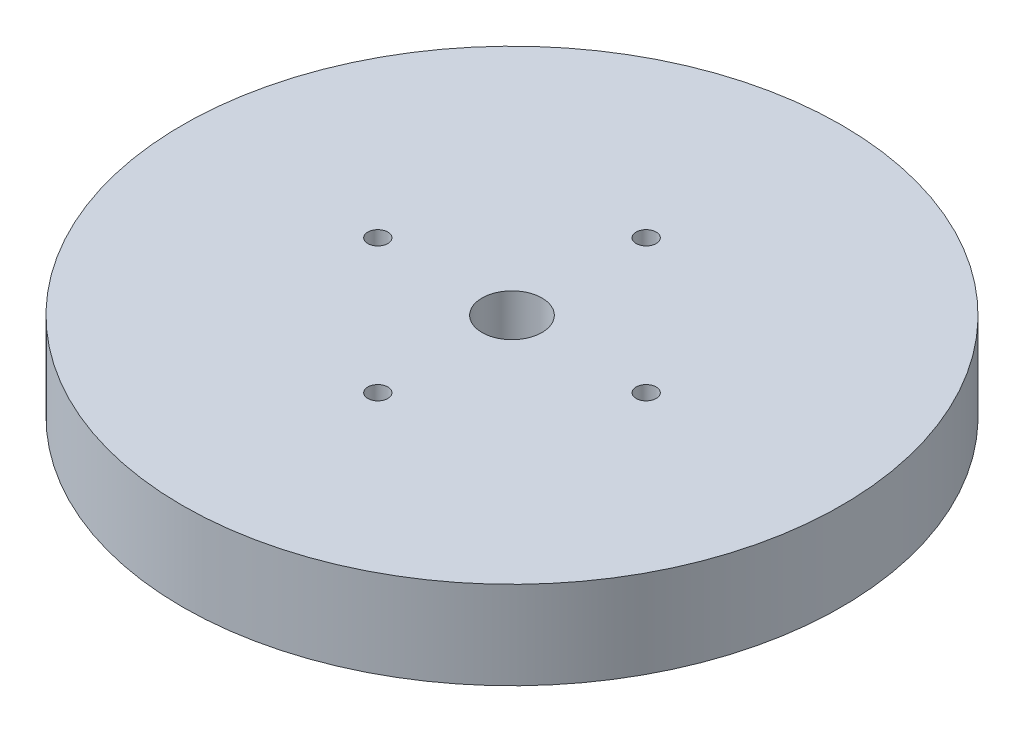
SolidWorks part; units mm, degrees
ref_plane "Front Plane" through (0, 0, 0) normal (0, 0, 1) x (1, 0, 0)
ref_plane "Top Plane" through (0, 0, 0) normal (0, 1, 0) x (1, 0, 0)
ref_plane "Right Plane" through (0, 0, 0) normal (1, 0, 0) x (0, 0, -1)
sketch "Sketch1" plane through (0, 0, 0) normal (0, 1, 0) x (1, 0, 0)
  circle A0 centre (0, 0) radius 82.5
  dimension "FLANGE_OD" = 165
extrude "Boss-Extrude1" add sketch "Sketch1" along normal blind 22
sketch "Sketch2" plane through (0, 0, 0) normal (0, 1, 0) x (1, 0, 0)
  circle A0 centre (0, 0) radius 7.5
  dimension "BORE_D" = 15
extrude "Cut-Extrude1" cut sketch "Sketch2" along normal through all
sketch "Sketch3" plane through (0, 22, 0) normal (0, 1, 0) x (1, 0, 0)
  circle A0 centre (0, 0) radius 33.5867 construction
  circle A1 centre (-33.5867, 0) radius 2.506
  dimension "BOLT_D" = 5.0121
  dimension "BOLT_PCD" = 67.1734
extrude "Cut-Extrude2" cut sketch "Sketch3" against normal blind 15.3164
pattern_circular "CirPattern1" count 4 over 360 about axis through (0, 0, 0) along (0, 1, 0) of "Cut-Extrude2"
